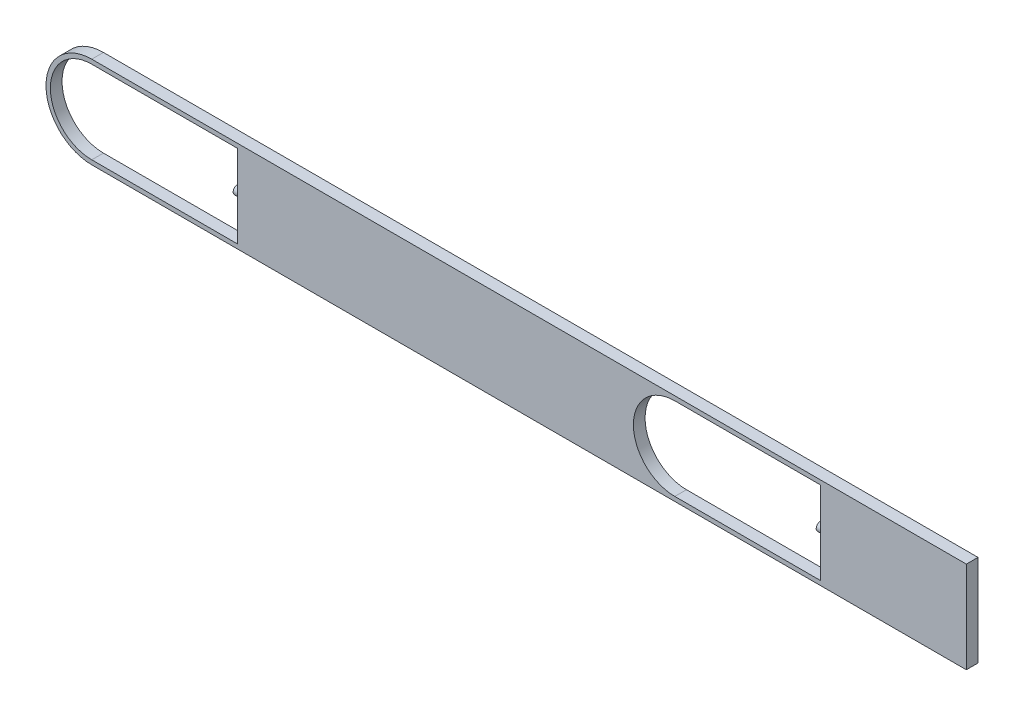
SolidWorks part; units mm, degrees
other "second"
other "first"
ref_plane "Front Plane" through (0, 0, 0) normal (0, 0, 1) x (1, 0, 0)
ref_plane "Top Plane" through (0, 0, 0) normal (0, 1, 0) x (1, 0, 0)
ref_plane "Right Plane" through (0, 0, 0) normal (1, 0, 0) x (0, 0, -1)
sketch "Sketch1" plane through (0, 0, 0) normal (0, 0, 1) x (1, 0, 0)
  circle A0 centre (0, 0) radius 19.939
  dimension "D1" = 39.878
extrude "circle extrude" add sketch "Sketch1" along normal blind 5.08
sketch "Sketch3" plane through (0, 0, 0) normal (1, 0, 0) x (0, 0, -1)
  line L0 (0, 55) -> (0, -55) construction
  line L1 (-5.08, 19.939) -> (0, 19.939)
  line L2 (-5.08, 19.939) -> (-5.08, -19.939)
  line L3 (-5.08, -19.939) -> (0, -19.939)
  line L4 (0, 19.939) -> (0, -19.939)
  line L5 (-5.08, -19.939) -> (0, -19.939) construction
extrude "rectangle extrude" add sketch "Sketch3" along normal blind 127
sketch "Sketch2" plane through (0, 0, 5.08) normal (0, 0, 1) x (1, 0, 0)
  circle A0 centre (0, 0) radius 18.034
  dimension "D1" = 36.068
extrude "circle cut" cut sketch "Sketch2" against normal through all
sketch "Sketch6" plane through (0, 0, 5.08) normal (0, 0, 1) x (1, 0, 0)
  line L1 (125.095, -18.034) -> (125.095, 18.034)
  line L3 (0, -18.034) -> (0, 18.034)
  line L4 (0, -18.034) -> (125.095, -18.034)
  line L5 (127, -19.939) -> (0, -19.939) construction
  line L6 (0, 18.034) -> (125.095, 18.034)
  line L8 (127, 19.939) -> (127, -19.939) construction
  arc A0 (0, 19.939) -> (0, -19.939) centre (0, 0) ccw construction
  circle A1 centre (0, 0) radius 18.034 construction
  point P5 (125.095, 0)
  point P12 (0, 0)
  point P17 (-19.939, 0)
  dimension "D1" = 1.905
  dimension "D2" = 1.905
  dimension "D3" = 19.939
extrude "rectangle cut" cut sketch "Sketch6" against normal through all
sketch "Sketch7" plane through (0, 0, 5.08) normal (0, 0, 1) x (1, 0, 0)
  line L1 (63.5, 18.034) -> (125.095, 18.034)
  line L2 (125.095, -18.034) -> (125.095, 18.034) construction
  line L3 (125.095, 18.034) -> (125.095, -18.034)
  line L4 (125.095, -18.034) -> (63.5, -18.034)
  line L5 (63.5, 18.034) -> (63.5, -18.034)
  line L6 (125.095, 18.034) -> (0, 18.034) construction
  dimension "D2" = 63.5
extrude "end shape" add sketch "Sketch7" against normal blind 5.08
sketch "Sketch8" plane through (63.5, 0, 0) normal (-1, 0, 0) x (0, 0, 1)
  circle A0 centre (2.54, 0) radius 1.905
  dimension "D1" = 3.81
  dimension "D2" = 2.54
extrude "for spring extrude" add sketch "Sketch8" along normal blind 2.54
pattern_linear "mirrored pattern" count 2 spacing 254 along (1, 0, 0) of bodies 109
sketch "Sketch10" plane through (127, 0, 0) normal (1, 0, 0) x (0, 0, -1)
  line L1 (-5.08, 19.939) -> (0, 19.939)
  line L2 (-5.08, 19.939) -> (-5.08, -19.939)
  line L3 (-5.08, -19.939) -> (0, -19.939)
  line L4 (0, 19.939) -> (0, -19.939)
extrude "Boss-Extrude1" add sketch "Sketch10" along normal up to next
